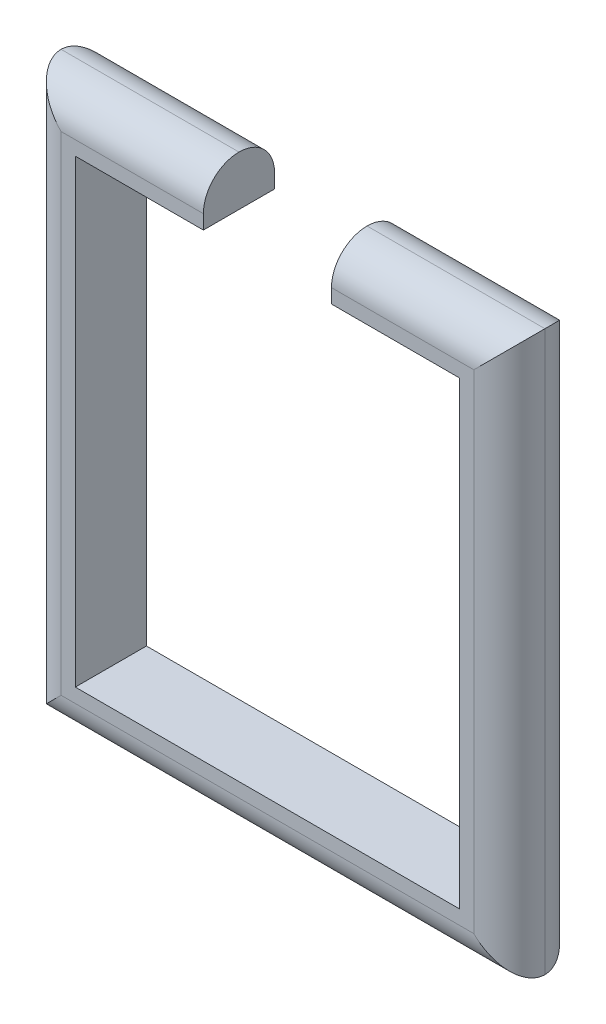
SolidWorks part; units mm, degrees
ref_plane "Front Plane" through (0, 0, 0) normal (0, 0, 1) x (1, 0, 0)
ref_plane "Top Plane" through (0, 0, 0) normal (0, 1, 0) x (1, 0, 0)
ref_plane "Right Plane" through (0, 0, 0) normal (1, 0, 0) x (0, 0, -1)
sketch "Sketch1" plane through (0, 0, 0) normal (0, 0, 1) x (1, 0, 0)
  line L5 (-84.3868, -173.723) -> (144.2132, -173.723)
  line L6 (-84.3868, -173.723) -> (-84.3868, -262.623)
  line L7 (-84.3868, -262.623) -> (144.2132, -262.623)
  line L8 (144.2132, -173.723) -> (144.2132, -262.623)
  line L9 (-312.9868, -262.623) -> (372.8132, -262.623)
  line L10 (-312.9868, -262.623) -> (-312.9868, -1083.297)
  line L11 (-312.9868, -1083.297) -> (372.8132, -1083.297)
  line L12 (372.8132, -262.623) -> (372.8132, -1083.297)
  line L13 (-401.8868, -173.723) -> (461.7132, -173.723)
  line L14 (-401.8868, -173.723) -> (-401.8868, -1172.197)
  line L15 (-401.8868, -1172.197) -> (461.7132, -1172.197)
  line L16 (461.7132, -173.723) -> (461.7132, -1172.197)
  point P5 (29.9132, -173.723)
  point P7 (29.9132, -1083.297)
  dimension "D1" = 88.9
  dimension "D2" = 88.9
  dimension "D3" = 88.9
  dimension "D4" = 88.9
  dimension "D5" = 228.6
  dimension "D7" = 820.674
  dimension "D8" = 685.8
extrude "Boss-Extrude1" add sketch "Sketch1" along normal blind 127 contours L16 L13 L8 L9 L12 L11 L10 L6 L14 L15 region at (-97.5882, -218.173, 0)
fillet "Fillet2" radius 63.5 10 edges at (302.9632, -173.723, 0) (302.9632, -173.723, 127) (-243.1368, -173.723, 0) (-243.1368, -173.723, 127) (-401.8868, -672.96, 127) (-401.8868, -672.96, 0) (461.7132, -672.96, 127) (461.7132, -672.96, 0) (29.9132, -1172.197, 0) (29.9132, -1172.197, 127)
